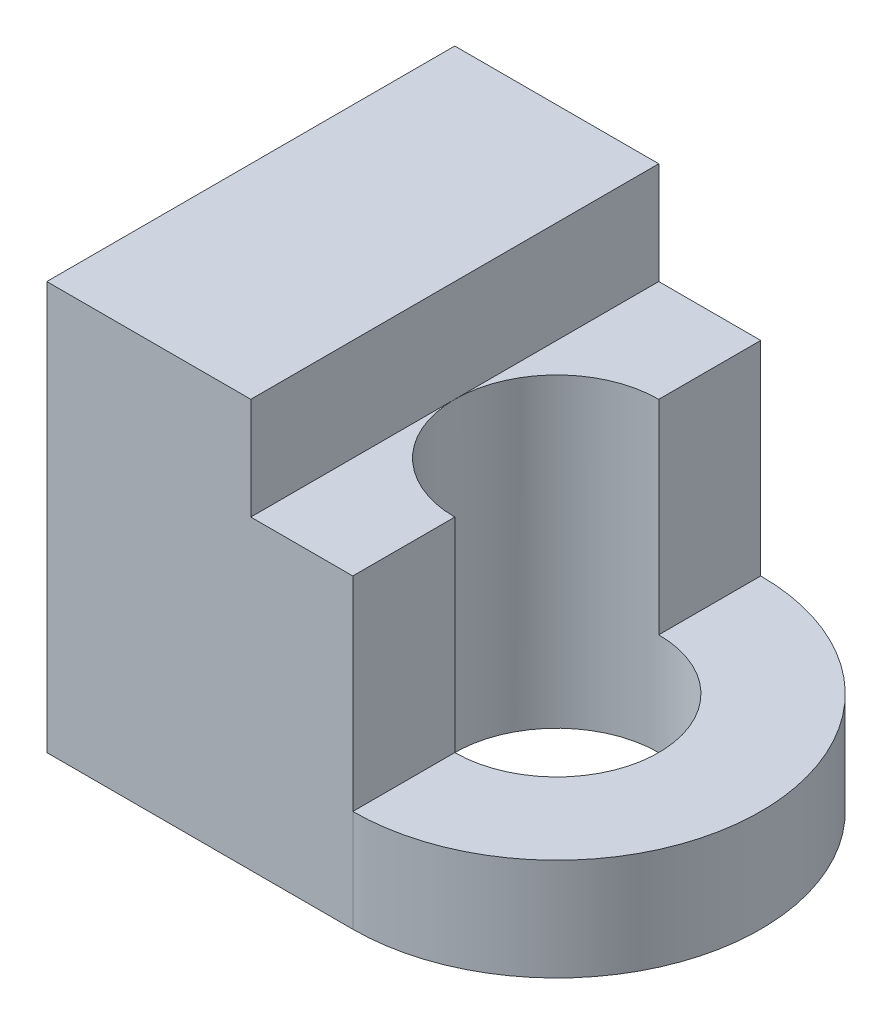
SolidWorks part; units mm, degrees
ref_plane "前基準面" through (0, 0, 0) normal (0, 0, 1) x (1, 0, 0)
ref_plane "上基準面" through (0, 0, 0) normal (0, 1, 0) x (1, 0, 0)
ref_plane "右基準面" through (0, 0, 0) normal (1, 0, 0) x (0, 0, -1)
sketch "草圖1" plane through (0, 0, 0) normal (0, 1, 0) x (1, 0, 0)
  line L0 (-5, -10) -> (-5, 10)
  line L1 (0, -10) -> (-15, -10)
  line L3 (0, 10) -> (-15, 10)
  line L4 (-15, -10) -> (-15, 10)
  line L5 (0, 5) -> (0, 10)
  line L6 (0, -5) -> (0, -10)
  circle A0 centre (0, 0) radius 5
  arc A1 (0, -10) -> (0, 10) centre (0, 0) ccw
  point P11 (-5, 0)
  dimension "D1" = 20
  dimension "D2" = 10
  dimension "D3" = 15
extrude "填料-伸長2" add sketch "草圖1" along normal blind 5 contours A0 | A1 L3 L4 L1 region at (0, 0, 0)
extrude "填料-伸長4" add sketch "草圖1<4>" along normal blind 15 contours A0 L0 L1 L6 | A0 L5 L3 L0 | L4 L1 L0 L3 region at (-10, 0, 0) region at (-2.7444, 0, 6.861) region at (-2.7444, 0, -6.861)
sketch "草圖1<4>" plane through (0, 0, 0) normal (0, 1, 0) x (1, 0, 0) same geometry as "草圖1"
extrude "填料-伸長5" add sketch "草圖1<5>" along normal blind 20 contours L4 L1 L0 L3 region at (-10, 0, 0)
sketch "草圖1<5>" plane through (0, 0, 0) normal (0, 1, 0) x (1, 0, 0) same geometry as "草圖1"
scale "縮放比例1" scale about centroid uniform scaling yes scale factor 0.2
